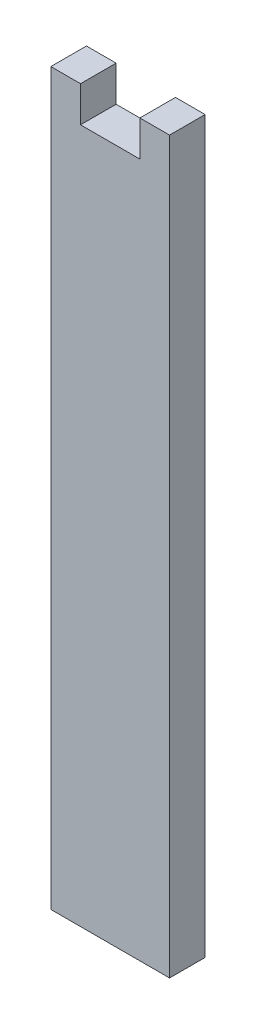
SolidWorks part; units mm, degrees
ref_plane "Front Plane" through (0, 0, 0) normal (0, 0, 1) x (1, 0, 0)
ref_plane "Top Plane" through (0, 0, 0) normal (0, 1, 0) x (1, 0, 0)
ref_plane "Right Plane" through (0, 0, 0) normal (1, 0, 0) x (0, 0, -1)
sketch "Sketch2" plane through (0, 0, 0) normal (0, 1, 0) x (1, 0, 0)
  line L0 (0, 0) -> (0, 6) construction
  dimension "D1" = 6
sketch "Sketch1" plane through (0, 0, 0) normal (0, 0, 1) x (1, 0, 0)
  line L0 (-5, 55.5) -> (0, 55.5)
  line L1 (-10, -61.5) -> (10, -61.5)
  line L2 (-10, -61.5) -> (-10, 61.5)
  line L3 (-10, 61.5) -> (10, 61.5)
  line L4 (10, -61.5) -> (10, 61.5)
  line L5 (-10, -61.5) -> (10, 61.5) construction
  line L6 (-10, 61.5) -> (10, -61.5) construction
  line L7 (10, 61.5) -> (5, 61.5)
  line L8 (10, 61.5) -> (10, 55.5)
  line L9 (10, 55.5) -> (5, 55.5)
  line L10 (5, 61.5) -> (5, 55.5)
  line L11 (-10, 61.5) -> (-5, 61.5)
  line L12 (-10, 61.5) -> (-10, 55.5)
  line L13 (-10, 55.5) -> (-5, 55.5)
  line L14 (-5, 61.5) -> (-5, 55.5)
  line L15 (0, 55.5) -> (5, 55.5)
  point P0 (0, 0)
  dimension "D1" = 20
  dimension "D2" = 123
  dimension "D3" = 6
extrude "Boss-Extrude1" add sketch "Sketch1" against normal up to vertex (6 mm away) contours L15 L0 L13 L2 L1 L4 L9 | L14 L3 L2 L13 | L3 L10 L9 L4 region at (0, -3, 0) region at (-7.5, 58.5, 0) region at (7.5, 58.5, 0) up to point (0, 0, -6)
equation "\"t_wood\"= 6' Thickness of the wood"
equation "\"t_glass\"= 2.5'Thickness of glass panels"
equation "\"w_glass\"= 181"
equation "\"h_glass\"= 151"
equation "\"h_food_internal\" = 60"
equation "\"entry_height\"= 20"
equation "\"entry diameter\"= 8"
equation "\"glass_bottom_overlap\"= 8"
equation "\"default_finger_size\"= 12"
equation "\"brood_depth\"= 42"
equation "\"outer_box_depth\" = \"brood_depth\" + ( 2 * \"t_glass\" ) + ( 2 * \"t_wood\" )"
equation "\"outer_box_width\"= \"w_glass\" + ( 2 * \"t_wood\" )"
equation "\"food_top_clearance\"= 10"
equation "\"outer_box_height\"= \"t_wood\" + \"h_glass\" + \"t_wood\" + \"h_food_internal\" + \"food_top_clearance\" + \"t_wood\""
equation "\"food_internal_depth\"= \"brood_depth\" + \"t_glass\" + \"t_glass\" - \"t_wood\" - \"t_wood\""
equation "\"food_channel_clearance_width\"= 14"
equation "\"bar_top_play\"= 0.5"
equation "\"bar_entry_angle\"= 10"
equation "\"bar_width\"= 20"
equation "\"entry_disk_play\"= 0.3"
equation "\"D1@Sketch2\"=\"t_wood\""
equation "\"D1@Sketch1\"=\"bar_width\""
equation "\"D2@Sketch1\"=\"h_glass\"-\"entry_height\"-\"entry diameter\""
equation "\"D3@Sketch1\"=\"t_wood\""
